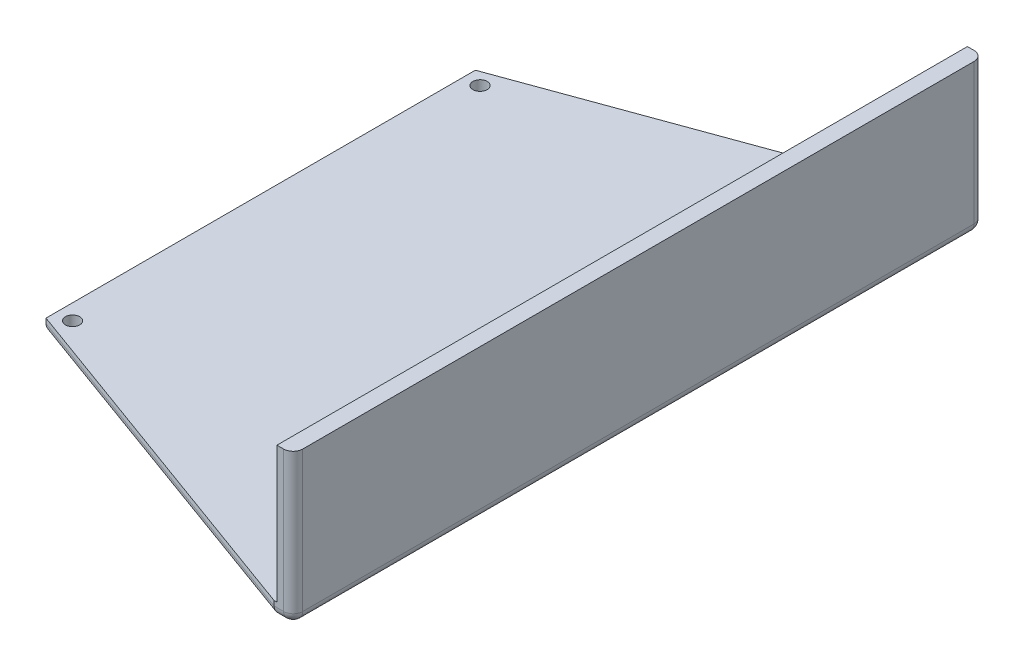
SolidWorks part; units mm, degrees
material "ABS"
ref_plane "Front Plane" through (0, 0, 0) normal (0, 0, 1) x (1, 0, 0)
ref_plane "Top Plane" through (0, 0, 0) normal (0, 1, 0) x (1, 0, 0)
ref_plane "Right Plane" through (0, 0, 0) normal (1, 0, 0) x (0, 0, -1)
sketch "Sketch1" plane through (0, 0, 0) normal (0, 1, 0) x (1, 0, 0)
  line L0 (-79.176, 45) -> (-79.176, -45)
  line L1 (-79.176, -45) -> (-4, -72.36)
  line L2 (-4, -72.36) -> (0, -72.36)
  line L3 (0, -72.36) -> (0, 72.36)
  line L4 (-79.176, 0) -> (0, 0) construction
  line L5 (-4, 72.36) -> (0, 72.36)
  line L6 (-79.176, 45) -> (-4, 72.36)
  dimension "D1" = 80
  dimension "D2" = 4
  dimension "D3" = 90
  dimension "D4" = 144.72
extrude "Boss-Extrude1" add sketch "Sketch1" along normal blind 3
sketch "Sketch2" plane through (0, 0, 0) normal (0, -1, 0) x (1, 0, 0)
  line L0 (-3.4, -72.36) -> (-3.4, 72.36)
  line L1 (0, -72.36) -> (-4, -72.36) construction
  line L2 (-4, 72.36) -> (0, 72.36) construction
  line L3 (0, 72.36) -> (0, -72.36) construction
  line L4 (-3.4, -72.36) -> (0, -72.36)
  line L5 (0, -72.36) -> (0, 72.36)
  line L6 (0, 72.36) -> (-3.4, 72.36)
  dimension "D1" = 3.4
extrude "Boss-Extrude2" add sketch "Sketch2" against normal blind 31.5
sketch "Sketch3" plane through (0, 3, 0) normal (0, 1, 0) x (1, 0, 0)
  line L0 (-79.176, -45) -> (-47.4658, -22.7963) construction
  line L4 (-79.176, 45) -> (-79.176, -45) construction
  line L5 (0, 0) -> (-79.176, 0) construction
  line L6 (0, -72.36) -> (0, 72.36) construction
  line L7 (-79.176, 45) -> (-47.4658, 22.7963) construction
  circle A0 centre (-75.8994, -42.7057) radius 1.5
  circle A1 centre (-75.8994, 42.7057) radius 1.5
  dimension "D2" = 3
  dimension "D1" = 55
  dimension "D3" = 4
extrude "Cut-Extrude1" cut sketch "Sketch3" against normal blind 40
fillet "Fillet1" radius 2 6 edges at (-79.176, 0, 0) (-41.588, 0, 58.68) (-2, 0, 72.36) (0, 0, 0) (-2, 0, -72.36) (-41.588, 0, -58.68)
fillet "Fillet2" radius 2 4 edges at (-0.5858, 0.5858, 71.7742) (-0.5858, 0.5858, -71.7742) (0, 16.75, 72.36) (0, 16.75, -72.36)
